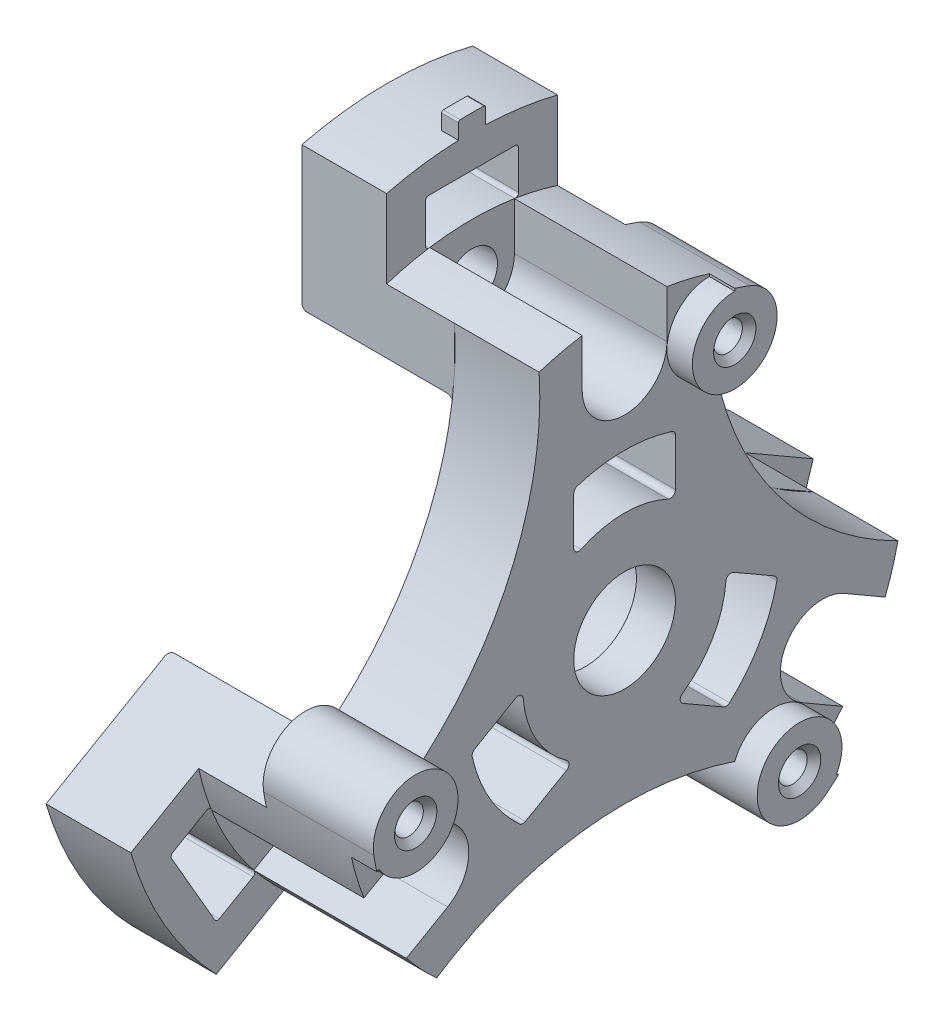
SolidWorks part; units mm, degrees
ref_plane "Front" through (0, 0, 0) normal (0, 0, 1) x (1, 0, 0)
ref_plane "Top" through (0, 0, 0) normal (0, 1, 0) x (1, 0, 0)
ref_plane "Right" through (0, 0, 0) normal (1, 0, 0) x (0, 0, -1)
sketch "草图1" plane through (0, 0, 0) normal (0, 0, 1) x (1, 0, 0)
  line L0 (-65.7429, 0) -> (89.5714, 0) construction
  line L1 (0, 67.1143) -> (0, -71.9143) construction
  line L2 (-7, 6) -> (-5, 6)
  line L3 (-5, 6) -> (-5, 16.5)
  line L4 (-5, 16.5) -> (0, 16.5)
  line L5 (0, 16.5) -> (0, 3)
  line L6 (-2.3, 3.975) -> (-7, 3.975)
  line L7 (-7, 3.975) -> (-7, 6)
  line L8 (-2.3, 3.975) -> (-2.3, 3)
  line L9 (-2.3, 3) -> (0, 3)
  dimension "D1" = 6
  dimension "D2" = 4.7
  dimension "D3" = 7.95
  dimension "D4" = 7
  dimension "D5" = 5
  dimension "D6" = 12
  dimension "D7" = 33
  dimension "D8" = 2.3
revolve "旋转1" add sketch "草图1" angle 360 about L0
sketch "草图2" plane through (-5, 0, 0) normal (-1, 0, 0) x (0, 0, 1)
  line L0 (-23.9515, 0) -> (26.381, 0) construction
  line L1 (0, 44.3891) -> (0, -20.5254) construction
  line L2 (0, 0) -> (-21.2641, -12.2768) construction
  line L3 (0, 0) -> (20.7932, -12.005) construction
  line L4 (0, 0) -> (-61.1055, 35.2793) construction
  line L5 (-5, 31.2128) -> (-5, 9) construction
  line L6 (5, 31.2128) -> (5, 9) construction
  circle A1 centre (-25, 14.4338) radius 20
  point P7 (0, 9)
  point P9 (-7.6795, 4.4338)
  dimension "D6" = 40
  dimension "D1" = 120
  dimension "D2" = 120
  dimension "D3" = 9
  dimension "D5" = 60
  dimension "D7" = 10
extrude "切除-拉伸1" cut sketch "草图2" against normal blind 10 contours A1
pattern_circular "阵列(圆周)1" count 3 over 360 about axis through (0, 0, 0) along (1, 0, 0) of "切除-拉伸1"
sketch "草图3" plane through (-5, 0, 0) normal (-1, 0, 0) x (0, 0, 1)
  line L0 (0, 18) -> (0, -12.9057) construction
  line L1 (-20.442, 0) -> (20.8303, 0) construction
  line L2 (-3, 8.4806) -> (-3, 5.6921)
  line L4 (3, 8.4806) -> (3, 5.6921)
  arc A0 (2.791, 8.7664) -> (-2.791, 8.7664) centre (0, 0) ccw
  circle A1 centre (0, 0) radius 6 construction
  arc A2 (2.5714, 5.421) -> (-2.5714, 5.421) centre (0, 0) ccw
  arc A3 (3, 5.6921) -> (2.5714, 5.421) centre (2.7, 5.6921) cw
  arc A4 (-2.5714, 5.421) -> (-3, 5.6921) centre (-2.7, 5.6921) cw
  arc A5 (3, 8.4806) -> (2.791, 8.7664) centre (2.7, 8.4806) ccw
  arc A6 (-2.791, 8.7664) -> (-3, 8.4806) centre (-2.7, 8.4806) ccw
  point P11 (3, 5.1962)
  point P16 (-3, 5.1962)
  point P19 (3, 8.6971)
  point P22 (-3, 8.6971)
  dimension "D1" = 9.2
  dimension "D3" = 0.3
  dimension "D2" = 6
extrude "切除-拉伸2" cut sketch "草图3" against normal blind 10
pattern_circular "阵列(圆周)2" count 3 over 360 about axis through (0, 0, 0) along (1, 0, 0) of "切除-拉伸2"
sketch "草图4" plane through (-5, 0, 0) normal (-1, 0, 0) x (0, 0, 1)
  line L0 (-16.7535, 0) -> (15.8993, 0) construction
  line L1 (0, 19.3876) -> (0, -16.6742) construction
  line L2 (-5.0408, 15.7111) -> (-5.0408, 11.9286)
  line L4 (5.0408, 11.9286) -> (5.0408, 15.7111)
  circle A0 centre (0, 0) radius 13.5 construction
  arc A1 (5.0408, 15.7111) -> (-5.0408, 15.7111) centre (0, 0) ccw construction
  arc A2 (5.0408, 15.7111) -> (-5.0408, 15.7111) centre (0, 0) ccw
  circle A3 centre (0, 13.5) radius 1.5
  arc A4 (-2.6744, 12.6708) -> (2.6744, 12.6708) centre (0, 13.5) ccw
  arc A5 (-2.6744, 12.6708) -> (-5.0408, 11.9286) centre (0, 0) ccw
  arc A6 (5.0408, 11.9286) -> (2.6744, 12.6708) centre (0, 0) ccw
  dimension "D1" = 27
  dimension "D2" = 3
  dimension "D4" = 5.6
  dimension "D5" = 25.9
extrude "凸台-拉伸1" add sketch "草图4" along normal blind 9
pattern_circular "阵列(圆周)3" count 3 over 360 about axis through (0, 0, 0) along (1, 0, 0) of "凸台-拉伸1"
sketch "草图5" plane through (-14, 0, 0) normal (-1, 0, 0) x (0, 0, 1)
  line L0 (-16.1323, 0) -> (16.637, 0) construction
  line L1 (0, 17.8058) -> (0, -12.3621) construction
  line L3 (-2.8, 12.6437) -> (-2.8, 9.2908)
  line L4 (-2.8, 9.2908) -> (2.8, 9.2908)
  line L5 (2.8, 12.6437) -> (2.8, 9.2908)
  arc A2 (2.8, 12.6437) -> (-2.8, 12.6437) centre (0, 0) ccw
  point P10 (0, 9.2908)
  point P11 (0, 13.55)
  dimension "D1" = 5.6
  dimension "D2" = 25.9
extrude "切除-拉伸3" cut sketch "草图5" against normal blind 1.7 contours L4 L5 A2 L3
sketch "草图10" plane through (-5, 0, 0) normal (-1, 0, 0) x (0, 0, 1)
  point P1 (0, 0)
  dimension "D1" = 12.8775
pattern_circular "阵列(圆周)4" count 3 over 360 about axis through (-65.7429, 0, 0) along (-1, 0, 0) of "切除-拉伸3"
sketch "草图6" plane through (0, 0, 0) normal (1, 0, 0) x (0, 0, -1)
  line L0 (-17.245, 0) -> (20.4566, 0) construction
  line L1 (0, 20.1005) -> (0, -14.3306) construction
  line L2 (-2.5, 16.3095) -> (-2.5, 13.5)
  line L3 (2.5, 16.3095) -> (2.5, 13.5)
  circle A0 centre (0, 0) radius 13.5 construction
  arc A1 (5.0408, 15.7111) -> (-5.0408, 15.7111) centre (0, 0) ccw construction
  arc A3 (2.5, 16.3095) -> (-2.5, 16.3095) centre (0, 0) ccw
  arc A4 (-2.5, 13.5) -> (2.5, 13.5) centre (0, 13.5) ccw
  dimension "D1" = 27
  dimension "D3" = 5
  dimension "D2" = 5
extrude "切除-拉伸4" cut sketch "草图6" against normal blind 9
pattern_circular "阵列(圆周)5" count 3 over 360 about axis through (0, 0, 0) along (1, 0, 0) of "切除-拉伸4"
sketch "草图7" plane through (-5, 0, 0) normal (-1, 0, 0) x (0, 0, 1)
  line L0 (0, 19.1221) -> (0, -13.8647) construction
  line L1 (16.0973, 0) -> (-17.961, 0) construction
  line L2 (-5, 15.5767) -> (-5, 15.7242)
  arc A1 (-5.8929, 15.4118) -> (-5, 15.5767) centre (-5, 13.0767) ccw
  circle A5 centre (0, 0) radius 14 construction
  arc A6 (-2.5, 16.3095) -> (-5.0408, 15.7111) centre (0, 0) ccw construction
  arc A7 (-5, 15.7242) -> (-5.8929, 15.4118) centre (0, 0) ccw
  point P7 (-5, 13.0767)
  dimension "D1" = 28
  dimension "D3" = 5
  dimension "D2" = 5
extrude "凸台-拉伸2" add sketch "草图7" against normal blind 6.5 contours A1 L2 A7
sketch "草图9" plane through (1.5, 0, 0) normal (1, 0, 0) x (0, 0, -1)
  line L0 (0, 17.5729) -> (0, -10.6538) construction
  line L1 (-14.0745, 0) -> (16.4041, 0) construction
  circle A0 centre (0, 0) radius 14 construction
  circle A1 centre (5, 13.0767) radius 0.85
  dimension "D1" = 1.7
extrude "切除-拉伸7" cut sketch "草图9" against normal blind 6.4 contours A1
chamfer "倒角3" distance 0.4 angle 45 1 edges at (1.5, 13.0767, -5.85)
pattern_circular "阵列(圆周)8" count 3 over 360 about axis through (0, 0, 0) along (1, 0, 0) of "凸台-拉伸2", "切除-拉伸7", "倒角3"
chamfer "倒角4" distance 0.3 angle 60 1 edges at (-7, 0, 3.975)
fillet "圆角6" radius 0.5 9 edges at (-5, 12.3565, -3.8754) (-5, 10.7, 0) (-5, 12.3565, 3.8754) (-5, -9.5345, -8.7633) (-5, -5.35, -9.2665) (-5, -2.822, -12.6388) (-5, -2.822, 12.6388) (-5, -5.35, 9.2665) (-5, -9.5345, 8.7633)
fillet "圆角7" radius 0.5 1 edges at (-7, 0, 6)
sketch "草图11" plane through (-14, 0, 0) normal (-1, 0, 0) x (0, 0, 1)
  line L0 (-24.0343, 0) -> (27.0991, 0) construction
  line L1 (0, 23.8854) -> (0, -19.7008) construction
  line L2 (-5.0408, 15.7111) -> (-5.0408, 20.3345)
  line L3 (5.0408, 15.7111) -> (5.0408, 20.3345)
  line L4 (-2.55, 19) -> (2.55, 19)
  line L5 (-2.75, 18.8) -> (-2.75, 16.2692)
  line L7 (2.75, 18.8) -> (2.75, 16.2692)
  arc A0 (5.0408, 20.3345) -> (0, 20.95) centre (0, 0) ccw
  arc A1 (5.0408, 15.7111) -> (-5.0408, 15.7111) centre (0, 0) ccw construction
  arc A2 (5.0408, 15.7111) -> (2.75, 16.2692) centre (0, 0) ccw
  arc A3 (-2.75, 16.2692) -> (-5.0408, 15.7111) centre (0, 0) ccw
  arc A4 (0, 20.95) -> (-5.0408, 20.3345) centre (0, 0) ccw
  arc A5 (2.75, 18.8) -> (2.55, 19) centre (2.55, 18.8) ccw
  arc A6 (-2.75, 18.8) -> (-2.55, 19) centre (-2.55, 18.8) cw
  point P15 (0, 17)
  point P16 (0, 19)
  point P18 (2.75, 19)
  point P20 (0, 22)
  point P23 (-2.75, 19)
  dimension "D1" = 41.9
  dimension "D4" = 0.2
  dimension "D2" = 5.5
  dimension "D3" = 19
extrude "凸台-拉伸3" add sketch "草图11" against normal up to surface (5 mm away) up to face at (-9, 13.5, -1.5)
pattern_circular "阵列(圆周)9" count 3 over 360 about axis through (0, 0, 0) along (1, 0, 0) of "凸台-拉伸3"
sketch "草图12" plane through (-9, 0, 0) normal (1, 0, 0) x (0, 0, -1)
  line L0 (0, 23.0537) -> (0, -15.9342) construction
  line L1 (-23.5138, 0) -> (22.1093, 0) construction
  line L2 (-0.8, 21.8388) -> (-0.8, 20.9347)
  line L3 (0.8, 21.8388) -> (0.8, 20.9347)
  arc A0 (0.7032, 21.9387) -> (-0.7032, 21.9387) centre (0, 0) ccw
  arc A1 (5.0408, 20.3345) -> (-5.0408, 20.3345) centre (0, 0) ccw construction
  arc A2 (0.8, 20.9347) -> (-0.8, 20.9347) centre (0, 0) ccw
  arc A3 (-21.95, 0) -> (21.95, 0) centre (0, 0) ccw
  arc A4 (-0.8, 21.8388) -> (-0.7032, 21.9387) centre (-0.7, 21.8388) cw
  arc A5 (0.7032, 21.9387) -> (0.8, 21.8388) centre (0.7, 21.8388) cw
  dimension "D2" = 1
  dimension "D3" = 0.1
  dimension "D1" = 1.6
extrude "凸台-拉伸4" add sketch "草图12" against normal blind 1 contours A0 A4 L2 A2 L3 A5
pattern_circular "阵列(圆周)10" [suppressed] count 3 over 360
fillet "圆角9" radius 0.3 6 edges at (-14, -9.0734, -9.2399) (-14, -3.4653, -12.4777) (-14, 12.5387, -3.2378) (-14, 12.5387, 3.2378) (-14, -9.0734, 9.2399) (-14, -3.4653, 12.4777)
fillet "圆角10" radius 0.2 6 edges at (-11.5, 16.2692, -2.75) (-11.5, 16.2692, 2.75) (-11.5, -10.5162, -12.7146) (-11.5, -5.753, -15.4646) (-11.5, -5.753, 15.4646) (-11.5, -10.5162, 12.7146)
